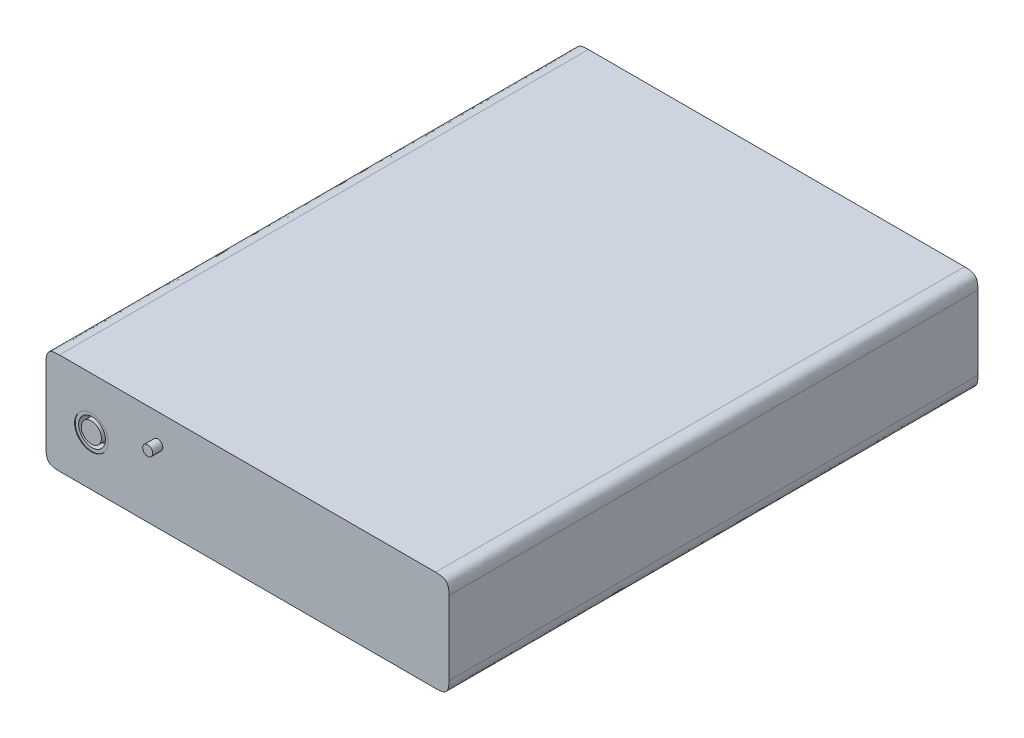
SolidWorks part; units mm, degrees
ref_plane "Front Plane" through (0, 0, 0) normal (0, 0, 1) x (1, 0, 0)
ref_plane "Top Plane" through (0, 0, 0) normal (0, 1, 0) x (1, 0, 0)
ref_plane "Right Plane" through (0, 0, 0) normal (1, 0, 0) x (0, 0, -1)
sketch "Sketch1" plane through (0, 0, 0) normal (0, 1, 0) x (1, 0, 0)
  line L1 (-76.2, -100.0125) -> (76.2, -100.0125)
  line L2 (-76.2, -100.0125) -> (-76.2, 100.0125)
  line L3 (-76.2, 100.0125) -> (76.2, 100.0125)
  line L4 (76.2, -100.0125) -> (76.2, 100.0125)
  line L5 (-76.2, -100.0125) -> (76.2, 100.0125) construction
  line L6 (-76.2, 100.0125) -> (76.2, -100.0125) construction
  point P0 (0, 0)
  dimension "D1" = 152.4
  dimension "D2" = 200.025
extrude "Boss-Extrude1" add sketch "Sketch1" along normal blind 38.1
fillet "Fillet1" radius 5.08 1 edges at (-76.2, 38.1, 0) conic radius 2.54
fillet "Fillet2" radius 5.08 1 edges at (76.2, 38.1, 0) conic radius 2.54
fillet "Fillet3" radius 5.08 1 edges at (-76.2, 0, 0) conic radius 2.54
fillet "Fillet4" radius 5.08 1 edges at (76.2, 0, 0) conic radius 2.54
sketch "Sketch2" plane through (0, 0, 100.0125) normal (0, 0, 1) x (1, 0, 0)
  circle A0 centre (-59.039, 18.7357) radius 6.35
  dimension "D1" = 12.7
sketch "Sketch3" plane through (0, 0, 100.0125) normal (0, 0, 1) x (1, 0, 0)
  circle A0 centre (-59.039, 18.7357) radius 5.08
  dimension "D1" = 10.16
extrude "Cut-Extrude1" cut sketch "Sketch3" against normal blind 3.81
extrude "Cut-Extrude2" cut sketch "Sketch2" against normal blind 0.254 contours A0
sketch "Sketch4" plane through (0, 0, 96.2025) normal (0, 0, 1) x (1, 0, 0)
  circle A0 centre (-59.039, 18.7357) radius 3.81
  dimension "D1" = 7.62
extrude "Boss-Extrude3" add sketch "Sketch4" along normal blind 3.81
sketch "Sketch5" plane through (0, 0, 100.0125) normal (0, 0, 1) x (1, 0, 0)
  circle A0 centre (-33.9336, 27.2873) radius 1.905
  dimension "D1" = 3.81
extrude "Boss-Extrude4" add sketch "Sketch5" along normal blind 3.81
